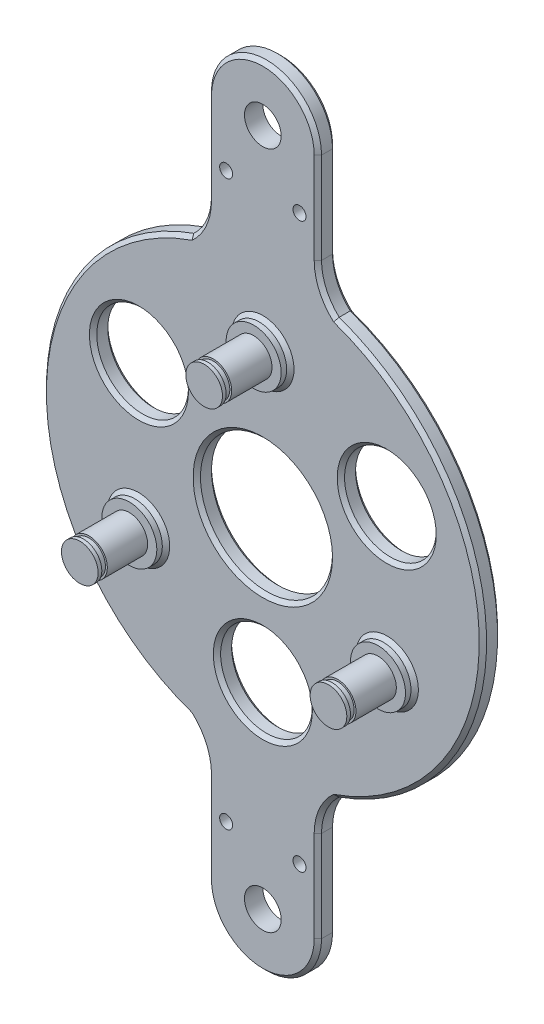
SolidWorks part; units mm, degrees
ref_plane "Front Plane" through (0, 0, 0) normal (0, 0, 1) x (1, 0, 0)
ref_plane "Top Plane" through (0, 0, 0) normal (0, 1, 0) x (1, 0, 0)
ref_plane "Right Plane" through (0, 0, 0) normal (1, 0, 0) x (0, 0, -1)
ref_axis "X AXIS" through (-88.99, 0, 0) along (1, 0, 0)
ref_axis "Y AXIS" through (0, 55, 0) along (0, -1, 0)
ref_axis "Z AXIS" through (0, 0, -88.99) along (0, 0, 1)
sketch "Sketch1" plane through (0, 0, 0) normal (0, 0, 1) x (1, 0, 0)
  line L1 (0, 0) -> (0, 47.625) construction
  line L2 (0, 55) -> (0, -55) construction
  line L3 (0, 0) -> (-41.2445, -23.8125) construction
  line L4 (0, 0) -> (41.2445, -23.8125) construction
  circle A2 centre (0, 0) radius 76.2
  dimension "D4" = 152.4
  dimension "D1" = 120
  dimension "D2" = 120
  dimension "D3" = 47.625
extrude "Boss-Extrude1" add sketch "Sketch1" against normal blind 6.35
sketch "Sketch2" plane through (0, 0, 0) normal (0, 0, 1) x (1, 0, 0)
  line L0 (0, 55) -> (0, -55) construction
  circle A0 centre (0, 49.7078) radius 6.35
  dimension "D1" = 12.7
  dimension "D2" = 49.7078
extrude "Boss-Extrude2" add sketch "Sketch2" along normal blind 20.32
pattern_circular "CirPattern1" count 3 over 360 about axis through (0, 0, 0) along (0, 0, 1) of "Boss-Extrude2"
sketch "Sketch3" plane through (0, 0, 20.32) normal (0, 0, 1) x (1, 0, 0)
  circle A0 centre (0, 49.7078) radius 4.7625
  dimension "D1" = 9.525
hole_wizard "5/8 (0.625) Diameter Hole1" positions "Sketch7" profile "Sketch8" hole size "5/8" standard "ANSI Inch" end condition up to next
sketch "Sketch7" plane through (0, 0, 0) normal (0, 0, 1) x (1, 0, 0)
  point P0 (0, 0)
sketch "Sketch8" plane through (0, 0, 0) normal (1, 0, 0) x (0, -1, 0)
  line L0 (0, 0) -> (0, 6.35)
  line L1 (0, 6.35) -> (7.9375, 6.35)
  line L2 (7.9375, 6.35) -> (7.9375, 0)
  line L5 (7.9375, 0) -> (0, 0)
  line L11 (0, -6.35) -> (0, 107.95) construction
  dimension "Thru Hole Dia." = 15.875
  dimension "Thru Hole Depth" = 6.35
sketch "Sketch11" plane through (0, 0, 0) normal (0, 0, 1) x (1, 0, 0)
  circle A0 centre (0, 49.7078) radius 9.525
  dimension "D1" = 19.05
extrude "Boss-Extrude3" add sketch "Sketch11" along normal blind 3.175
pattern_circular "CirPattern5" count 3 over 360 about axis through (0, 0, 0) along (0, 0, 1) of "Boss-Extrude3"
sketch "Sketch12" plane through (0, 0, 0) normal (0, 0, 1) x (1, 0, 0)
  circle A0 centre (0, 0) radius 22.86
  dimension "D1" = 45.72
extrude "Cut-Extrude3" cut sketch "Sketch12" against normal up to next
sketch "Sketch13" plane through (0, 0, 0) normal (1, 0, 0) x (0, 0, -1)
  line L0 (-3.175, 56.0578) -> (-20.32, 56.0578) construction
  line L1 (-3.175, 56.0578) -> (-20.32, 56.0578) construction
  line L2 (-20.32, 49.7078) -> (-25.655, 49.7078) construction
  line L3 (-19.05, 55.4228) -> (-17.145, 55.4228)
  line L4 (-19.05, 55.4228) -> (-19.05, 56.6928)
  line L5 (-19.05, 56.6928) -> (-17.145, 56.6928)
  line L6 (-17.145, 55.4228) -> (-17.145, 56.6928)
  line L7 (-19.05, 55.4228) -> (-17.145, 56.6928) construction
  line L8 (-19.05, 56.6928) -> (-17.145, 55.4228) construction
  line L9 (-20.32, 54.4703) -> (-20.32, 44.9453) construction
  line L10 (-20.32, 49.7078) -> (-3.175, 49.7078) construction
  point P2 (-18.0975, 56.0578)
  dimension "D1" = 11.43
  dimension "D2" = 1.905
  dimension "D3" = 13.97
revolve "Cut-Revolve1" cut sketch "Sketch13" angle 360 about L2
pattern_circular "CirPattern6" count 3 over 360 about axis through (0, 0, 0) along (0, 0, 1) of "Cut-Revolve1"
chamfer "Chamfer1" distance 1.27 angle 45 7 edges at (76.2, 0, 0) (9.525, 49.7078, 0) (-47.8107, -16.605, 0) (38.2857, -33.1028, 0) (22.86, 0, 0) (76.2, 0, -6.35) (22.86, 0, -6.35)
sketch "Sketch14" plane through (0, 0, 0) normal (0, 0, 1) x (1, 0, 0)
  line L0 (0, 0) -> (65.9911, 38.1) construction
  line L1 (0, 0) -> (43.0482, -24.8539) construction
  circle A0 centre (0, 0) radius 76.2 construction
  circle A1 centre (42.8942, 24.765) radius 15.875
  circle A3 centre (0, 0) radius 22.86 construction
  dimension "D2" = 31.75
  dimension "D3" = 26.67
  dimension "D1" = 60
extrude "Cut-Extrude4" cut sketch "Sketch14" against normal up to next
pattern_circular "CirPattern7" count 3 over 360 about axis through (0, 0, 0) along (0, 0, 1) of "Cut-Extrude4"
chamfer "Chamfer2" distance 1.27 angle 45 6 edges at (15.875, -49.53, -6.35) (58.7692, 24.765, -6.35) (-27.0192, 24.765, -6.35) (-7.9375, -63.2782, 0) (-50.8317, 38.5132, 0) (58.7692, 24.765, 0)
sketch "Sketch15" plane through (0, 0, 0) normal (0, 0, 1) x (1, 0, 0)
  line L0 (0, 0) -> (0, 136.525) construction
  line L2 (-19.05, 72.4679) -> (19.05, 72.4679)
  line L3 (-19.05, 72.4679) -> (-19.05, 136.525)
  line L4 (-19.05, 136.525) -> (19.05, 136.525)
  line L5 (19.05, 72.4679) -> (19.05, 136.525)
  circle A1 centre (0, 0) radius 74.93 construction
  dimension "D1" = 136.525
  dimension "D2" = 38.1
extrude "Boss-Extrude4" add sketch "Sketch15" against normal blind 6.35
fillet "Fillet1" 2 edges at (-19.05, 136.525, -3.175) (19.05, 136.525, -3.175) type full round first side face at (-19.05, 94.2578, -3.3867) second side face at (19.05, 94.2578, -2.9633) middle face at (0, 136.525, -3.175)
sketch "Sketch16" plane through (0, 0, 0) normal (0, 0, 1) x (1, 0, 0)
  line L0 (-19.05, 117.475) -> (-19.05, 72.4679) construction
  line L1 (-19.05, 85.9106) -> (-19.05, 72.4679)
  arc A0 (-30.377, 68.4963) -> (-19.05, 85.9106) centre (-38.1, 85.9106) ccw
  arc A1 (-19.05, 72.4679) -> (19.05, 72.4679) centre (0, 0) ccw construction
  arc A2 (-19.05, 72.4679) -> (-30.377, 68.4963) centre (0, 0) ccw
  dimension "D1" = 38.1
extrude "Boss-Extrude5" add sketch "Sketch16" against normal blind 6.35
mirror "Mirror1" about plane through (0, 0, 0) normal (1, 0, 0) of "Boss-Extrude5"
hole_wizard "#10 (0.5) Diameter Hole1" positions "Sketch17" profile "Sketch18" hole size "#10" standard "ANSI Inch" end condition through all
sketch "Sketch17" plane through (0, 0, 0) normal (0, 0, 1) x (1, 0, 0)
  point P0 (0, 117.475)
sketch "Sketch18" plane through (0, 117.475, 0) normal (1, 0, 0) x (0, -1, 0)
  line L0 (0, 0) -> (0, 6.35)
  line L1 (0, 6.35) -> (6.35, 6.35)
  line L2 (6.35, 6.35) -> (6.35, 0)
  line L5 (6.35, 0) -> (0, 0)
  line L11 (0, -6.35) -> (0, 107.95) construction
  dimension "Thru Hole Dia." = 12.7
  dimension "Thru Hole Depth" = 6.35
sketch "Sketch19" plane through (0, 0, 0) normal (0, 0, 1) x (1, 0, 0)
  line L0 (0, 0) -> (-12.7, 97.6022) construction
  line L1 (0, 0) -> (12.7, 97.6022) construction
  line L2 (0, 0) -> (0, 136.525) construction
  circle A0 centre (0, 0) radius 98.425 construction
  arc A1 (19.05, 117.475) -> (-19.05, 117.475) centre (0, 117.475) ccw construction
  circle A2 centre (-12.7, 97.6022) radius 2.3812
  circle A3 centre (12.7, 97.6022) radius 2.3812
  dimension "D1" = 196.85
  dimension "D4" = 4.7625
  dimension "D2" = 12.7
  dimension "D3" = 12.7
hole_wizard "CSK for #8 Flat Head Machine Screw (100)1" positions "Sketch20" profile "Sketch21" countersink size "#8" standard "ANSI Inch" end condition through all
sketch "Sketch20" plane through (0, 0, -6.35) normal (0, 0, -1) x (-1, 0, 0)
  point P0 (12.7, 97.6022)
  point P3 (-12.7, 97.6022)
sketch "Sketch21" plane through (-12.7, 97.6022, -6.35) normal (1, 0, 0) x (0, 1, 0)
  line L0 (0, 0) -> (0, 26.67)
  line L1 (0, 26.67) -> (2.2479, 26.67)
  line L2 (2.2479, 26.67) -> (2.2479, 1.6518)
  line L3 (2.2479, 1.6518) -> (4.2164, 0)
  line L5 (4.2164, 0) -> (0, 0)
  line L6 (-2.2479, 1.6518) -> (-4.2164, 0) construction
  line L11 (0, -6.35) -> (0, 107.95) construction
  dimension "Thru Hole Dia." = 4.4958
  dimension "Thru Hole Depth" = 26.67
  dimension "Near C'Sink Dia." = 8.4328
  dimension "Near C'Sink Angle" = 100
mirror "Mirror3" about plane through (0, 0, 0) normal (0, 1, 0) of "CSK for #8 Flat Head Machine Screw (100)1", "#10 (0.5) Diameter Hole1", "Mirror1", "Boss-Extrude5", "Fillet1", "Boss-Extrude4"
chamfer "Chamfer3" distance 1.27 angle 45 16 edges at (22.1309, -75.5236, -6.35) (19.05, -101.6928, -6.35) (0, -136.525, -6.35) (22.1309, -75.5236, 0) (19.05, -101.6928, 0) (0, -136.525, 0) (22.1309, 75.5236, 0) (-22.1309, 75.5236, 0) (19.05, 101.6928, 0) (-19.05, 101.6928, 0) (0, 136.525, 0) (-22.1309, 75.5236, -6.35) (22.1309, 75.5236, -6.35) (-19.05, 101.6928, -6.35) (19.05, 101.6928, -6.35) (0, 136.525, -6.35)
